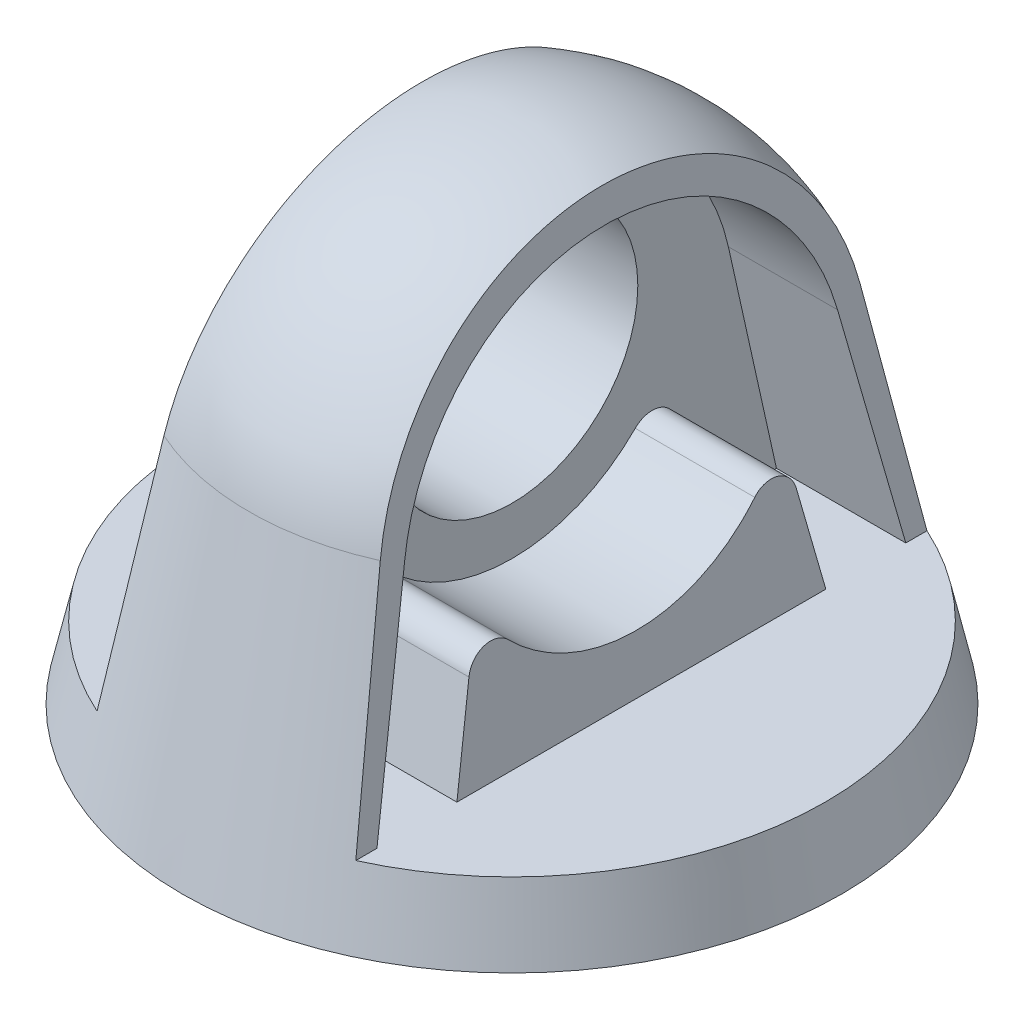
SolidWorks part; units mm, degrees
ref_plane "Front Plane" through (0, 0, 0) normal (0, 0, 1) x (1, 0, 0)
ref_plane "Top Plane" through (0, 0, 0) normal (0, 1, 0) x (1, 0, 0)
ref_plane "Right Plane" through (0, 0, 0) normal (1, 0, 0) x (0, 0, -1)
sketch "Sketch2" plane through (0, 0, 0) normal (0, 0, 1) x (1, 0, 0)
  line L0 (0, 85) -> (0, -70.7348) construction
  line L1 (0, 0) -> (-55, 0)
  line L2 (0, 0) -> (0, 85)
  line L3 (-43.9259, 49.7731) -> (-55, 0)
  arc A0 (0, 85) -> (-43.9259, 49.7731) centre (0, 40) ccw
  dimension "D3" = 45
  dimension "D1" = 55
  dimension "D2" = 85
revolve "Revolve3" add sketch "Sketch2" angle 360 about L0
sketch "Sketch6" plane through (0, 0, 0) normal (0, 0, 1) x (1, 0, 0)
  line L0 (0, 0) -> (0, 85) construction
  line L1 (-52.3301, 12) -> (-23.2129, 12)
  line L2 (-43.9259, 49.7731) -> (-55, 0) construction
  line L3 (-23.2129, 12) -> (-15, 82.4264)
  line L4 (52.3301, 12) -> (21.5933, 12)
  line L5 (55, 0) -> (43.9259, 49.7731) construction
  line L6 (21.5933, 12) -> (15, 82.4264)
  line L7 (-55, 0) -> (55, 0) construction
  arc A0 (43.9259, 49.7731) -> (-43.9259, 49.7731) centre (0, 40) ccw construction
  arc A1 (-15, 82.4264) -> (15, 82.4264) centre (0, 40) cw
  dimension "D1" = 30
  dimension "D2" = 15
  dimension "D3" = 12
  dimension "D4" = 12
  dimension "D5" = 15
  dimension "D6" = 12
extrude "Cut-Extrude1" cut sketch "Sketch6" along normal through all and the other way through all flip side to cut
sketch "Sketch7" plane through (0, 0, 0) normal (1, 0, 0) x (0, 0, -1)
  line L4 (47.6673, 12) -> (-47.6673, 12) construction
  line L5 (44.1345, 12) -> (-44.1345, 12)
  line L6 (47.1909, -1.7374) -> (36.1169, 48.0357)
  line L7 (-36.1169, 48.0357) -> (-47.1909, -1.7374)
  line L8 (44.1345, 12) -> (36.1169, 48.0357)
  line L9 (-36.1169, 48.0357) -> (-44.1345, 12)
  line L10 (-55, 0) -> (55, 0) construction
  line L11 (-27.3163, 27.6117) -> (-30.7898, 12)
  line L12 (0, 50) -> (0, 38.7921) construction
  line L13 (27.3163, 27.6117) -> (30.7898, 12)
  circle A2 centre (0, 50) radius 21
  arc A3 (36.1169, 48.0357) -> (-36.1169, 48.0357) centre (0, 40) ccw
  arc A4 (36.1169, 48.0357) -> (-36.1169, 48.0357) centre (0, 40) ccw
  arc A5 (-20.574, 29.562) -> (20.574, 29.562) centre (0, 50) ccw
  arc A6 (27.3163, 27.6117) -> (20.574, 29.562) centre (23.4118, 26.743) ccw
  arc A7 (-20.574, 29.562) -> (-27.3163, 27.6117) centre (-23.4118, 26.743) ccw
  point P17 (25.4347, 36.0689)
  point P24 (-25.4347, 36.0689)
  dimension "D2" = 42
  dimension "D4" = 29
  dimension "D5" = 4
  dimension "D3" = 50
  dimension "D1" = 8
extrude "Cut-Extrude4" cut sketch "Sketch7" along normal through all and the other way blind 36 contours A2
extrude "Cut-Extrude7" cut sketch "Sketch7<10>" along normal through all contours A7 A5 A6 L13 L5 L8 A4 L9 L11 A2 | A2 region at (0, 13.0962, -37.4621)
sketch "Sketch7<10>" plane through (0, 0, 0) normal (1, 0, 0) x (0, 0, -1) same geometry as "Sketch7"
mirror "Mirror1" about plane through (0, 0, 0) normal (1, 0, 0) of "Cut-Extrude1"
